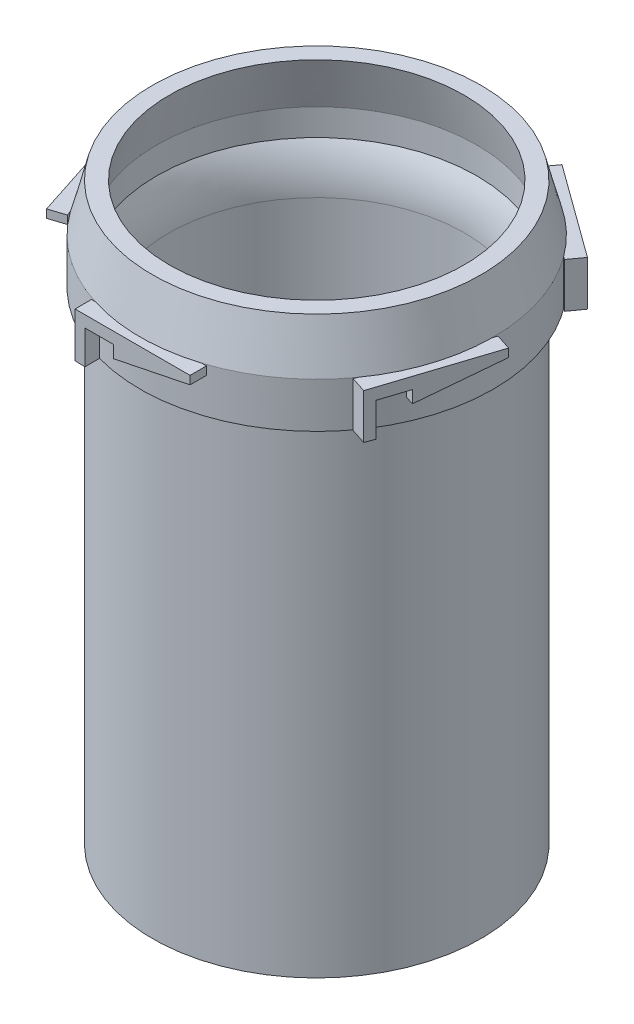
SolidWorks part; units mm, degrees
ref_plane "Front Plane" through (0, 0, 0) normal (0, 0, 1) x (1, 0, 0)
ref_plane "Top Plane" through (0, 0, 0) normal (0, 1, 0) x (1, 0, 0)
ref_plane "Right Plane" through (0, 0, 0) normal (1, 0, 0) x (0, 0, -1)
sketch "Sketch1" plane through (0, 0, 0) normal (0, 0, 1) x (1, 0, 0)
  line L1 (20, 0) -> (20, 58.6905)
  line L2 (20, 58.6905) -> (21.5, 58.6905)
  line L3 (21.5, 58.6905) -> (21.5, 64.1905)
  line L4 (21.5, 64.1905) -> (20, 70)
  line L6 (0, 70) -> (20, 70)
  line L7 (0, 0) -> (0, 109.187) construction
  line L9 (19, 0) -> (19, 1.5)
  line L10 (19, 1.5) -> (5, 1.5)
  line L11 (5, 1.5) -> (5, 2.9386)
  line L12 (5, 2.9386) -> (0, 2.9386)
  line L13 (0, 70) -> (0, 2.9386)
  line L14 (19, 0) -> (20, 0)
  dimension "D1" = 1.5
  dimension "D2" = 5.5
  dimension "D3" = 6
  dimension "D4" = 20
  dimension "D5" = 70
  dimension "D6" = 1
  dimension "D7" = 1.5
  dimension "D8" = 5
revolve "Revolve1" add sketch "Sketch1" angle 360 about L7
shell "Shell5" thickness 2 removed face at (0, 70, -20)
fillet "Fillet1" radius 10 1 edges at (0, 60.6905, -18)
ref_plane "Plane1" through (0, 0, 21.5) normal (0, 0, 1) x (1, 0, 0)
sketch "Sketch4" plane through (0, 0, 21.5) normal (0, 0, 1) x (1, 0, 0)
  line L0 (-6.9244, 58.7234) -> (-5.7244, 58.6905)
  line L2 (-6.9244, 64.1905) -> (-6.9244, 58.7234)
  line L6 (-6.9244, 64.1905) -> (7.0756, 64.1905)
  line L7 (-20, 58.6905) -> (20, 58.6905) construction
  line L8 (-5.7244, 58.6905) -> (-5.7244, 62.7905)
  line L9 (-5.7244, 62.7905) -> (-2.2244, 62.7905)
  line L10 (-2.2244, 62.7905) -> (-2.2244, 61.2905)
  line L11 (-2.2244, 61.2905) -> (7.0756, 63.1905)
  line L12 (7.0756, 63.1905) -> (7.0756, 64.1905)
  line L13 (21.5, 64.1905) -> (-21.5, 64.1905) construction
  line L14 (7.0756, 64.1905) -> (-6.9244, 64.1905)
  line L15 (-6.9244, 64.1905) -> (-6.9244, 58.7234)
  point P0 (0, 61.2018)
  dimension "D1" = 1.2
  dimension "D2" = 1.4
  dimension "D3" = 1.5
  dimension "D4" = 1
  dimension "D5" = 3.5
  dimension "D6" = 14
extrude "Boss-Extrude1" add sketch "Sketch4" along normal blind 1 and the other way blind 1 contours L11 L12 L6 L2 L0 L8 L9 L10 region at (-1.0398, 62.8212, 21.5)
pattern_circular "CirPattern1" count 5 over 360 about axis through (0, 64.1905, 0) along (0, -1, 0) of "Boss-Extrude1"
